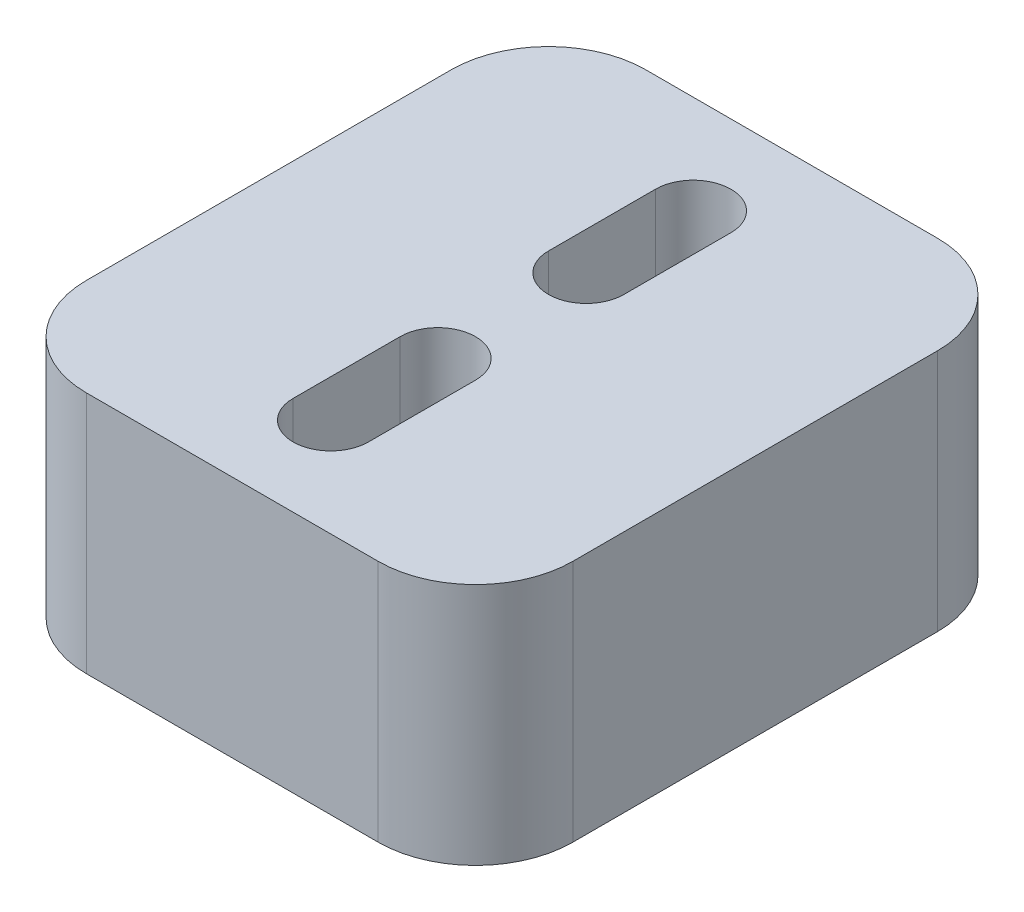
SolidWorks part; units mm, degrees
ref_plane "Front Plane" through (0, 0, 0) normal (0, 0, 1) x (1, 0, 0)
ref_plane "Top Plane" through (0, 0, 0) normal (0, 1, 0) x (1, 0, 0)
ref_plane "Right Plane" through (0, 0, 0) normal (1, 0, 0) x (0, 0, -1)
sketch "Sketch1" plane through (0, 0, 0) normal (0, 1, 0) x (1, 0, 0)
  line L0 (0, 7.45) -> (0, 3.05) construction
  line L1 (-10, -11.5) -> (10, -11.5)
  line L2 (-10, -11.5) -> (-10, 11.5)
  line L3 (-10, 11.5) -> (10, 11.5)
  line L4 (10, -11.5) -> (10, 11.5)
  line L5 (0, 11.5) -> (0, -11.5) construction
  line L6 (-10, 0) -> (10, 0) construction
  line L7 (1.55, 7.45) -> (1.55, 3.05)
  line L8 (-1.55, 7.45) -> (-1.55, 3.05)
  line L9 (0, -7.45) -> (0, -3.05) construction
  line L10 (1.55, -7.45) -> (1.55, -3.05)
  line L11 (-1.55, -7.45) -> (-1.55, -3.05)
  circle A4 centre (0, 5) radius 1.55 construction
  arc A6 (1.55, 7.45) -> (-1.55, 7.45) centre (0, 7.45) ccw
  arc A7 (-1.55, 3.05) -> (1.55, 3.05) centre (0, 3.05) ccw
  arc A8 (1.55, -7.45) -> (-1.55, -7.45) centre (0, -7.45) cw
  arc A9 (-1.55, -3.05) -> (1.55, -3.05) centre (0, -3.05) cw
  point P0 (0, 0)
  point P6 (0, 1.5)
  point P10 (0, 5.25)
  point P16 (0, -5.25)
  point P22 (0, 9)
  dimension "D1" = 1.5
  dimension "D2" = 5
  dimension "D5" = 3.1
  dimension "D3" = 20
  dimension "D4" = 23
  dimension "D6" = 2.5
extrude "Boss-Extrude1" add sketch "Sketch1" along normal blind 10
fillet "Fillet1" radius 4 4 edges at (-10, 5, 11.5) (-10, 5, -11.5) (10, 5, -11.5) (10, 5, 11.5)
